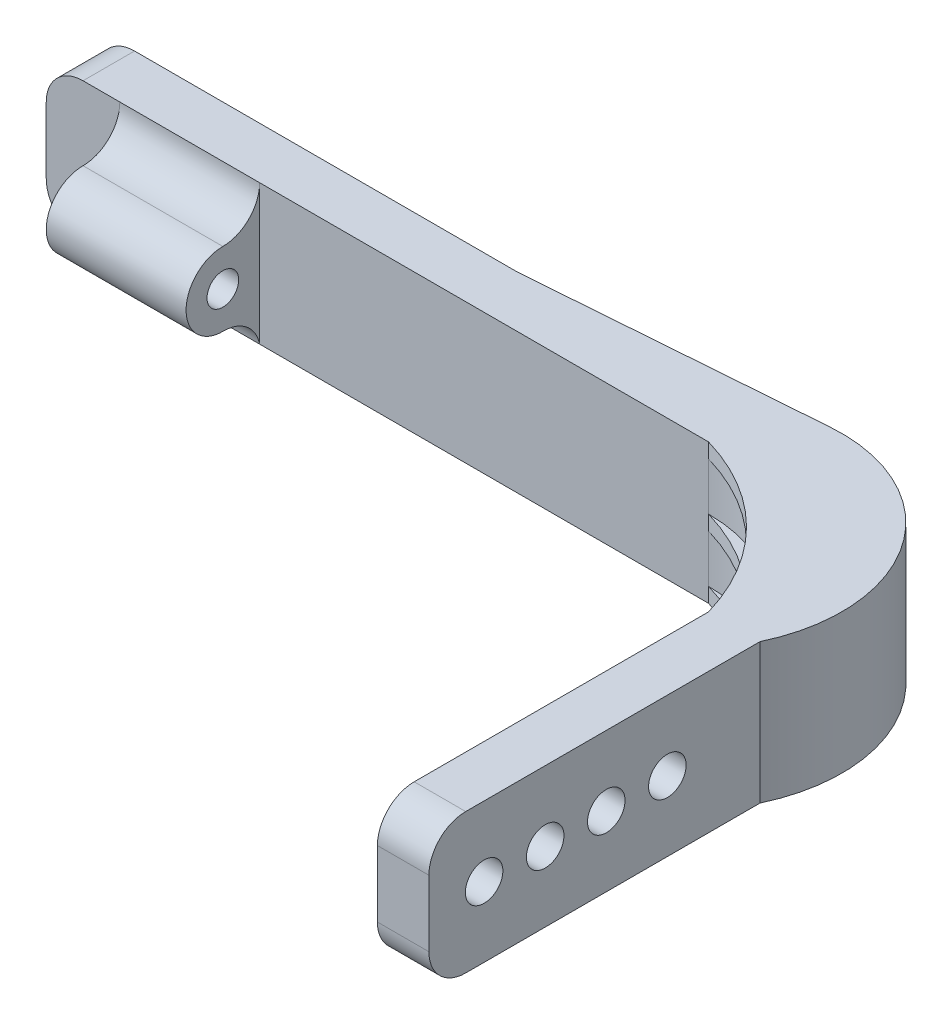
SolidWorks part; units mm, degrees
ref_plane "Front Plane" through (0, 0, 0) normal (0, 0, 1) x (1, 0, 0)
ref_plane "Top Plane" through (0, 0, 0) normal (0, 1, 0) x (1, 0, 0)
ref_plane "Right Plane" through (0, 0, 0) normal (1, 0, 0) x (0, 0, -1)
sketch "Sketch1" plane through (0, 0, 0) normal (0, 1, 0) x (1, 0, 0)
  line L0 (0, 0) -> (90, 0)
  line L1 (117, -27) -> (117, -72)
  line L2 (0, -7) -> (90, -7)
  line L3 (110, -27) -> (110, -72)
  line L4 (110, -72) -> (117, -72)
  line L5 (0, -7) -> (0, 0)
  arc A0 (90, 0) -> (117, -27) centre (90, -27) cw
  arc A1 (90, -7) -> (110, -27) centre (90, -27) cw
  dimension "D4" = 20
  dimension "D2" = 90
  dimension "D3" = 45
  dimension "D1" = 7
extrude "Boss-Extrude1" add sketch "Sketch1" along normal blind 19
ref_plane "Plane1" through (0, 0, 65) normal (0, 0, 1) x (1, 0, 0)
sketch "Sketch3" plane through (0, 0, 65) normal (0, 0, 1) x (1, 0, 0)
  line L6 (117, 11) -> (117, 7)
  line L8 (117, 19) -> (117, 0) construction
  line L9 (117, 7) -> (120, 4)
  line L10 (120, 4) -> (120, 14)
  line L11 (120, 14) -> (117, 11)
  line L12 (117, 9) -> (120, 9) construction
  line L13 (110, 19) -> (117, 19) construction
  dimension "D1" = 10
  dimension "D2" = 4
  dimension "D3" = 3
  dimension "D4" = 10
sketch "Sketch4" plane through (0, 0, 0) normal (1, 0, 0) x (0, 0, -1)
  line L1 (-72, 19) -> (-72, 0) construction
  line L2 (-72, 9.5) -> (2.8171, 9.5) construction
  line L3 (-72, 19) -> (-72, 0) construction
  circle A0 centre (-64.5, 9.5) radius 2.55
  dimension "D1" = 5.1
  dimension "D3" = 7.5
extrude "Cut-Extrude1" cut sketch "Sketch4" along normal through all
pattern_linear "LPattern1" count 4 spacing 8.3 along (0, 0, -1) of "Cut-Extrude1"
sketch "Sketch5" plane through (0, 0, 0) normal (0, 0, 1) x (1, 0, 0)
  line L0 (90, 19) -> (0, 19) construction
  line L1 (0, 19) -> (0, 0) construction
  circle A0 centre (15, 9) radius 2.55
  dimension "D1" = 5.1
  dimension "D2" = 10
  dimension "D3" = 15
fillet "Fillet2" radius 5 4 edges at (113.5, 0, 72) (113.5, 19, 72) (0, 0, 3.5) (0, 19, 3.5)
sketch "Sketch6" plane through (0, 0, 0) normal (0, 1, 0) x (1, 0, 0)
  line L0 (90, 0) -> (5, 0) construction
  line L1 (57.068, 0) -> (96.4605, 3)
  line L2 (90, 0) -> (57.068, 0)
  line L6 (110, -27) -> (110, -67)
  line L7 (110, -67) -> (117, -67)
  line L8 (117, -67) -> (117, -27)
  line L9 (90, 0) -> (5, 0)
  line L10 (5, 0) -> (5, -7)
  line L11 (5, -7) -> (90, -7)
  arc A0 (117, -27) -> (96.4605, 3) centre (98.0552, -17.9394) ccw
  arc A3 (117, -27) -> (90, 0) centre (90, -27) ccw
  arc A8 (117, -27) -> (90, 0) centre (90, -27) ccw
  arc A9 (110, -27) -> (90, -7) centre (90, -27) ccw
  dimension "D2" = 21
  dimension "D3" = 3
  dimension "D1" = 0
extrude "Boss-Extrude4" add sketch "Sketch6" along normal up to surface (19 mm away) up to face at (81.7168, 19, 24.0332)
sketch "Sketch8" plane through (0, 0, 0) normal (0, 1, 0) x (1, 0, 0)
  arc A0 (90, -7) -> (110, -27) centre (81.8988, -35.1012) cw
  arc A1 (90, -7) -> (110, -27) centre (90, -27) cw
extrude "Boss-Extrude5" add sketch "Sketch8" along normal blind 2
pattern_linear "LPattern3" count 3 spacing 8.5 along (0, 1, 0) of "Boss-Extrude5"
fillet "Fillet4" radius 20 1 edges at (57.068, 9.5, 0)
ref_plane "Plane2" through (10, 0, 0) normal (-1, 0, 0) x (0, 0, 1)
sketch "Sketch9" plane through (10, 0, 0) normal (-1, 0, 0) x (0, 0, 1)
  line L0 (2.3062, 9) -> (15.0365, 9) construction
  line L1 (0, 19) -> (7, 19) construction
  line L2 (7, 14) -> (12, 14)
  line L3 (7, 17) -> (7, 10.5) construction
  line L4 (7, 4) -> (12, 4)
  line L5 (7, 8.5) -> (7, 2) construction
  line L6 (7, 14) -> (7, 4)
  arc A0 (12, 14) -> (12, 4) centre (12, 9) cw
  circle A1 centre (12, 9) radius 2.15
  point P16 (17, 9)
  dimension "D6" = 5
  dimension "D7" = 4.3
  dimension "D1" = 10
  dimension "D2" = 5
  dimension "D3" = 5
  dimension "D4" = 5
  dimension "D5" = 5
  dimension "D8" = 5
extrude "Boss-Extrude6" add sketch "Sketch9" against normal blind 19
fillet "Fillet5" radius 5 2 edges at (19.5, 4, 7) (19.5, 14, 7)
